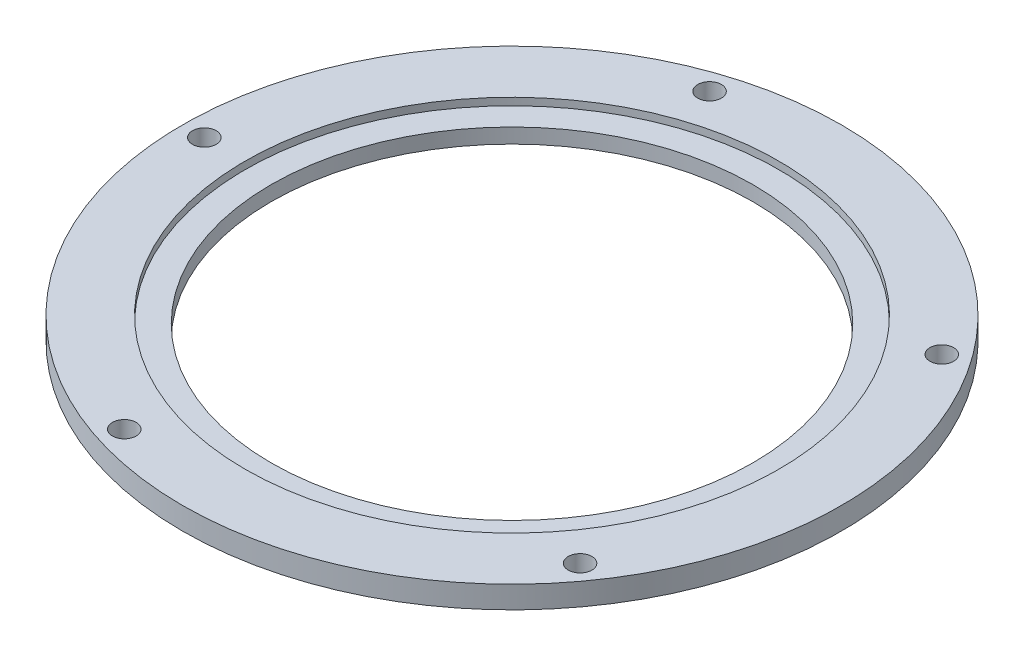
SolidWorks part; units mm, degrees
ref_plane "Front Plane" through (0, 0, 0) normal (0, 0, 1) x (1, 0, 0)
ref_plane "Top Plane" through (0, 0, 0) normal (0, 1, 0) x (1, 0, 0)
ref_plane "Right Plane" through (0, 0, 0) normal (1, 0, 0) x (0, 0, -1)
sketch "Sketch1" plane through (0, 0, 0) normal (0, 1, 0) x (1, 0, 0)
  circle A0 centre (0, 0) radius 44.45
  circle A1 centre (0, 0) radius 36
  circle A2 centre (0, 0) radius 32.5
  dimension "D1" = 88.9
  dimension "D2" = 72
  dimension "D3" = 65
extrude "Boss-Extrude1" add sketch "Sketch1" along normal blind 3 contours A0 A1 region at (-43.1928, 0, 0)
extrude "Boss-Extrude2" add sketch "Sketch1<3>" along normal blind 2 contours A1 A2 region at (-34.9818, 0, 0)
sketch "Sketch1<3>" plane through (0, 0, 0) normal (0, 1, 0) x (1, 0, 0) same geometry as "Sketch1"
hole_wizard "M3 Clearance Hole1" positions "Sketch2" profile "Sketch3" hole size "M3" standard "ANSI Metric" end condition through all
sketch "Sketch2" plane through (0, 3, 0) normal (0, 1, 0) x (1, 0, 0)
  line L1 (0, 0) -> (-41.5, 0) construction
  point P4 (-41.5, 0)
  dimension "D1" = 41.5
sketch "Sketch3" plane through (-41.5, 3, 0) normal (1, 0, 0) x (0, 0, 1)
  line L0 (0, 0) -> (0, 3)
  line L1 (0, 3) -> (1.6, 3)
  line L2 (1.6, 3) -> (1.6, 0)
  line L5 (1.6, 0) -> (0, 0)
  line L11 (0, -6.35) -> (0, 107.95) construction
  dimension "Thru Hole Dia." = 3.2
  dimension "Thru Hole Depth" = 3
pattern_circular "CirPattern1" count 5 over 360 about axis through (0, 3, 0) along (0, -1, 0) of "M3 Clearance Hole1" reverse direction yes
equation "\"Ratio\"= 15"
equation "\"Hull Diameter\"= 3.5in"
equation "\"Fixed Ring Diameter\"= 76"
equation "\"Fixed Pin Diameter\"= 6"
equation "\"Output Ring Diameter\"= 40"
equation "\"Output Pin Diameter\"= 6"
equation "\"Disk Bearing Inner Diameter\"= 9"
equation "\"Disk Bearing Outer Diameter\"= 17"
equation "\"Disk Bearing Height\"= 5"
equation "\"Shaft Bearing Inner Diameter\"= 15"
equation "\"Shaft Bearing Outer Diameter\"= 21"
equation "\"Shaft Bearing Height\"= 4"
equation "\"Eccentricity\"= 1.5"
equation "\"Disk Height\"= 8"
equation "\"Disk Spacing\"= 5"
equation "\"Hull Height\"= 40"
equation "\"Shaft End Bearing Inner Diameter\"= 12"
equation "\"Shaft End Bearing Outer Diameter\"= 18"
equation "\"Shaft End Bearing Height\"= 4"
equation "\"Output Bearing Inner Diameter\"= 55"
equation "\"Output Bearing Outer Diameter\"= 72"
equation "\"Outer Bearing Height\"= 9"
equation "\"D1@Sketch1\"=\"Hull Diameter\""
equation "\"D2@Sketch1\"=\"Output Bearing Outer Diameter\""
equation "\"D3@Sketch1\"=\"Output Bearing Inner Diameter\"+10"
